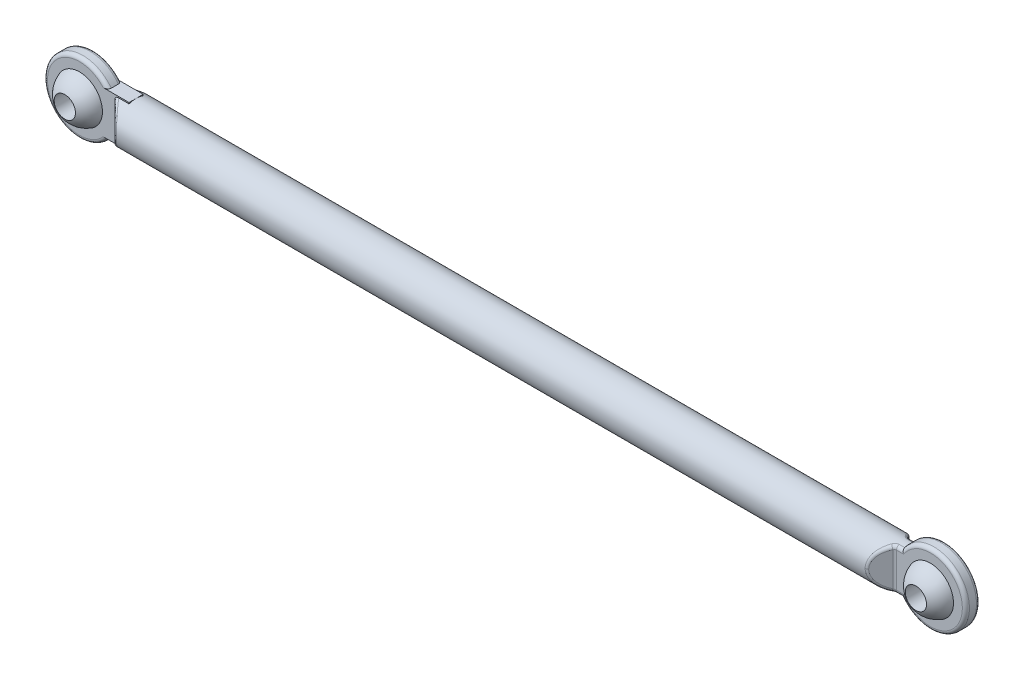
SolidWorks part; units mm, degrees
material "6063-T1"
ref_plane "前视基准面" through (0, 0, 0) normal (0, 0, 1) x (1, 0, 0)
ref_plane "上视基准面" through (0, 0, 0) normal (0, 1, 0) x (1, 0, 0)
ref_plane "右视基准面" through (0, 0, 0) normal (1, 0, 0) x (0, 0, -1)
other "Configuration Table"
sketch "草图1" plane through (0, 0, 0) normal (0, 0, 1) x (1, 0, 0)
  line L0 (0, 0) -> (120, 0) construction
  line L1 (0, 3) -> (120, 3)
  line L2 (0, -3) -> (120, -3)
  arc A2 (0, 3) -> (0, -3) centre (0, 0) ccw
  arc A3 (120, 3) -> (120, -3) centre (120, 0) cw
  dimension "D1" = 3
  dimension "D2" = 3
  dimension "D3" = 120
extrude "凸台-拉伸1" add sketch "草图1" along normal blind 1
sketch "草图2" plane through (0, 0, 1) normal (0, 0, 1) x (1, 0, 0)
  line L0 (120, 3) -> (0, 3) construction
  line L1 (7, 3) -> (113, 3)
  line L2 (7, 3) -> (7, -3)
  line L3 (7, -3) -> (113, -3)
  line L4 (113, 3) -> (113, -3)
  line L5 (0, -3) -> (120, -3) construction
  arc A2 (120, -3) -> (120, 3) centre (120, 0) ccw construction
  arc A5 (0, 3) -> (0, -3) centre (0, 0) ccw construction
  point P14 (123, 0)
  dimension "D1" = 10
  dimension "D2" = 7
extrude "凸台-拉伸2" add sketch "草图2" along normal blind 2
mirror "镜向2" about plane through (0, 0, 0) normal (0, 0, 1) of "凸台-拉伸2", "凸台-拉伸1"
sketch "草图3" plane through (7, 0, 0) normal (-1, 0, 0) x (0, 0, 1)
  circle A0 centre (0, 0) radius 3
  dimension "D1" = 6
extrude "切除-拉伸2" cut sketch "草图3" against normal blind 114 flip side to cut
sketch "草图4" plane through (0, 0, 1) normal (0, 0, 1) x (1, 0, 0)
  circle A0 centre (0, 0) radius 5
  circle A1 centre (120, 0) radius 5
  dimension "D1" = 10
  dimension "D2" = 10
extrude "凸台-拉伸3" add sketch "草图4" against normal blind 2
chamfer "倒角1" distance 2 angle 45 6 edges at (113, 0, 1) (113, 0, -3) (113, 0, -1) (7, 0, -1) (7, 0, -3) (7, 0, 1)
fillet "圆角2" radius 0.5 16 edges at (-5, 0, -1) (-5, 0, 1) (125, 0, 1) (125, 0, -1) (115.9958, 2.9944, -0.1834) (115.9958, -2.9944, 0.1834) (115, 0, 1) (115, 0, -1) (113.5505, 1.7321, 2.4495) (113.5505, -1.7321, 2.4495) (113.5505, 1.7321, -2.4495) (113.5505, -1.7321, -2.4495) (6.4495, -1.7321, -2.4495) (6.4495, 1.7321, -2.4495) (6.4495, -1.7321, 2.4495) (6.4495, 1.7321, 2.4495)
sketch "草图6" plane through (0, 0, 0) normal (0, 0, 1) x (1, 0, 0)
  line L0 (0, 3.4) -> (0, -3.4)
  arc A0 (0, 3.4) -> (0, -3.4) centre (0, 0) ccw
  dimension "D1" = 3.4
  dimension "D2" = 6.8
revolve "旋转2" add sketch "草图6" angle 360 about L0
sketch "草图7" plane through (0, 0, 0) normal (0, 0, 1) x (1, 0, 0)
  circle A0 centre (0, 0) radius 1.5
  dimension "D1" = 3
extrude "切除-拉伸3" cut sketch "草图7" against normal through all and the other way through all
ref_plane "基准面1" through (60, 0, 0) normal (1, 0, 0) x (0, 0, -1)
mirror "镜向3" about plane through (60, 0, 0) normal (1, 0, 0) of "切除-拉伸3", "旋转2"
